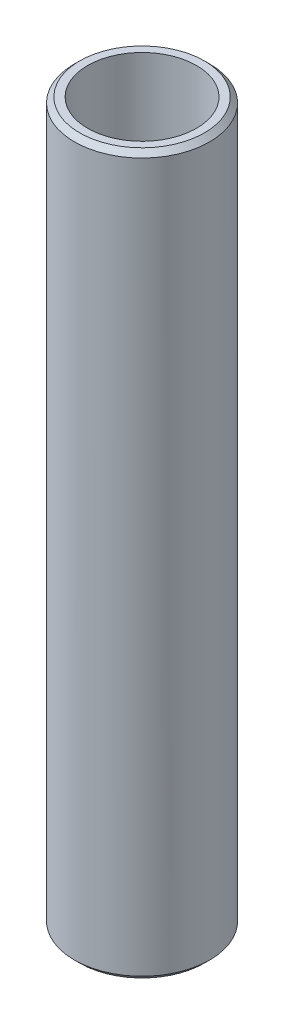
SolidWorks part; units mm, degrees
ref_plane "Front Plane" through (0, 0, 0) normal (0, 0, 1) x (1, 0, 0)
ref_plane "Top Plane" through (0, 0, 0) normal (0, 1, 0) x (1, 0, 0)
ref_plane "Right Plane" through (0, 0, 0) normal (1, 0, 0) x (0, 0, -1)
sketch "Sketch1" plane through (0, 0, 0) normal (0, 1, 0) x (1, 0, 0)
  circle A0 centre (0, 0) radius 32.5
  dimension "SHAFT_OD" = 65
extrude "Boss-Extrude1" add sketch "Sketch1" along normal blind 345.7464
sketch "Sketch2" plane through (0, 0, 0) normal (0, 1, 0) x (1, 0, 0)
  circle A0 centre (0, 0) radius 26.1776
  dimension "BORE_D" = 52.3553
extrude "Cut-Extrude1" cut sketch "Sketch2" along normal through all
chamfer "Chamfer1" distance 2.4994 angle 45 2 edges at (0, 345.7464, 32.5) (0, 0, 32.5)
